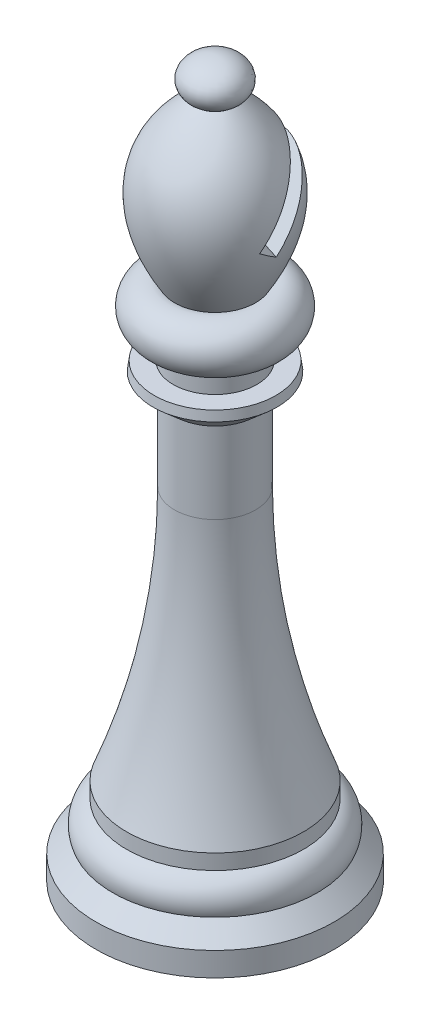
SolidWorks part; units mm, degrees
ref_plane "Front Plane" through (0, 0, 0) normal (0, 0, 1) x (1, 0, 0)
ref_plane "Top Plane" through (0, 0, 0) normal (0, 1, 0) x (1, 0, 0)
ref_plane "Right Plane" through (0, 0, 0) normal (1, 0, 0) x (0, 0, -1)
sketch "Sketch1" plane through (0, 0, 0) normal (0, 0, 1) x (1, 0, 0)
  line L0 (0, 0) -> (6.35, 0)
  line L1 (0, 0) -> (0, 38.1)
  line L2 (6.35, 0) -> (6.35, 1.27)
  line L3 (6.35, 1.27) -> (5.452, 2.168)
  line L4 (4.7193, 3.8079) -> (4.7193, 4.6182)
  line L5 (2.2307, 25.3036) -> (2.2307, 24.0336)
  line L6 (2.2307, 24.0336) -> (3.2428, 24.0336)
  line L7 (3.2428, 24.0336) -> (3.3118, 23.5303)
  line L8 (3.3118, 23.5303) -> (2.1629, 22.5289)
  line L9 (2.1629, 22.5289) -> (2.1629, 18.2109)
  line L10 (0, 38.1) -> (0, 38.1118)
  line L14 (0, 35.9659) -> (0, 38.1)
  arc A0 (5.452, 2.168) -> (4.7193, 3.8079) centre (4.2657, 2.6216) ccw
  arc A1 (2.1629, 27.7758) -> (2.2307, 25.3036) centre (2.4862, 26.5477) cw
  ellipse E0 centre (0, 37.0388) end of major axis (1.5231, 37.0388) minor radius 1.073 (1.0003, 36.2297) -> (0, 38.1118) ccw
  spline S0 degree 2 poles (4.7193, 4.6182) (2.1912, 11.1494) (2.1629, 18.2109) knots 0 0 0 1 1 1
  spline S1 degree 2 poles (1.0003, 36.2297) (5.2754, 32.9315) (2.1629, 27.7758) knots 0 0 0 1 1 1
  dimension "D5" = 1.27
  dimension "D6" = 4.318
  dimension "D10" = 1.27
  dimension "D1" = 6.35
  dimension "D2" = 38.1
  dimension "D3" = 1.27
  dimension "D4" = 1.27
  dimension "D7" = 1.27
  dimension "D8" = 0.508
  dimension "D9" = 1.524
revolve "Revolve1" add sketch "Sketch1" angle 360 about L1
sketch "Sketch2" plane through (0, 24.0336, 0) normal (0, 1, 0) x (1, 0, 0)
  line L0 (-2.2307, 0) -> (-3.2276, 0.3135)
  line L1 (-2.2307, 0) -> (-2.764, -1.6959)
  circle A1 centre (0, 0) radius 2.2307 construction
  circle A2 centre (0, 0) radius 3.2428 construction
ref_plane "Plane1" through (-3.2276, 24.0336, -0.3135) normal (-0.9539, 0, -0.3) x (-0.3, 0, 0.9539)
sketch "Sketch3" plane through (-3.2276, 24.0336, -0.3135) normal (-0.9539, 0, -0.3) x (-0.3, 0, 0.9539)
  line L0 (-3.2445, 10.5817) -> (-0.779, 7.0368)
  line L1 (-0.779, 7.0368) -> (-1.6131, 6.4566)
  line L2 (-1.6131, 6.4566) -> (-3.7885, 9.5845)
  arc A0 (-3.7885, 9.5845) -> (-3.2445, 10.5817) centre (-3.2672, 9.9471) cw
  spline S0 degree 3 poles (-1.6694, 12.1961) (-1.6869, 12.1825) (-1.7219, 12.1555) (-1.7737, 12.1146) (-1.875, 12.0336) (-2.0468, 11.8913) (-2.2868, 11.6781) (-2.5384, 11.4339) (-2.7732, 11.1831) (-2.9895, 10.9278) (-3.1844, 10.6719) (-3.3606, 10.4122) (-3.516, 10.1537) (-3.657, 9.8856) (-3.7802, 9.6129) (-3.8854, 9.3354) (-3.971, 9.0604) (-4.0396, 8.7815) (-4.0911, 8.4993) (-4.1259, 8.2113) (-4.1441, 7.9126) (-4.1443, 7.6073) (-4.1264, 7.2979) (-4.0892, 6.9706) (-4.0288, 6.6194) (-3.9407, 6.2426) (-3.8344, 5.8805) (-3.7147, 5.5351) (-3.5852, 5.2062) (-3.4388, 4.873) (-3.2633, 4.5107) (-3.108, 4.2192) (-2.9952, 4.0196) (-2.9462, 3.9346) (-2.9087, 3.8706) (-2.8707, 3.8064) (-2.845, 3.7636) (-2.8321, 3.7422) knots 0 0 0 0 0.006955 0.013873 0.020754 0.047676 0.083933 0.121578 0.157763 0.191803 0.22663 0.258768 0.290322 0.321325 0.353864 0.384265 0.414509 0.444275 0.47443 0.504568 0.535357 0.568372 0.600401 0.632651 0.671793 0.712299 0.754131 0.790262 0.827119 0.865112 0.904569 0.953523 0.968842 0.976566 0.984334 0.992145 1 1 1 1 construction
  point P7 (0, 0)
  dimension "D4" = 0.635
  dimension "D1" = 3.81
  dimension "D2" = 1.016
  dimension "D3" = 4.318
extrude "Cut-Extrude1" cut sketch "Sketch3" against normal blind 7.112 and the other way blind 5.842
